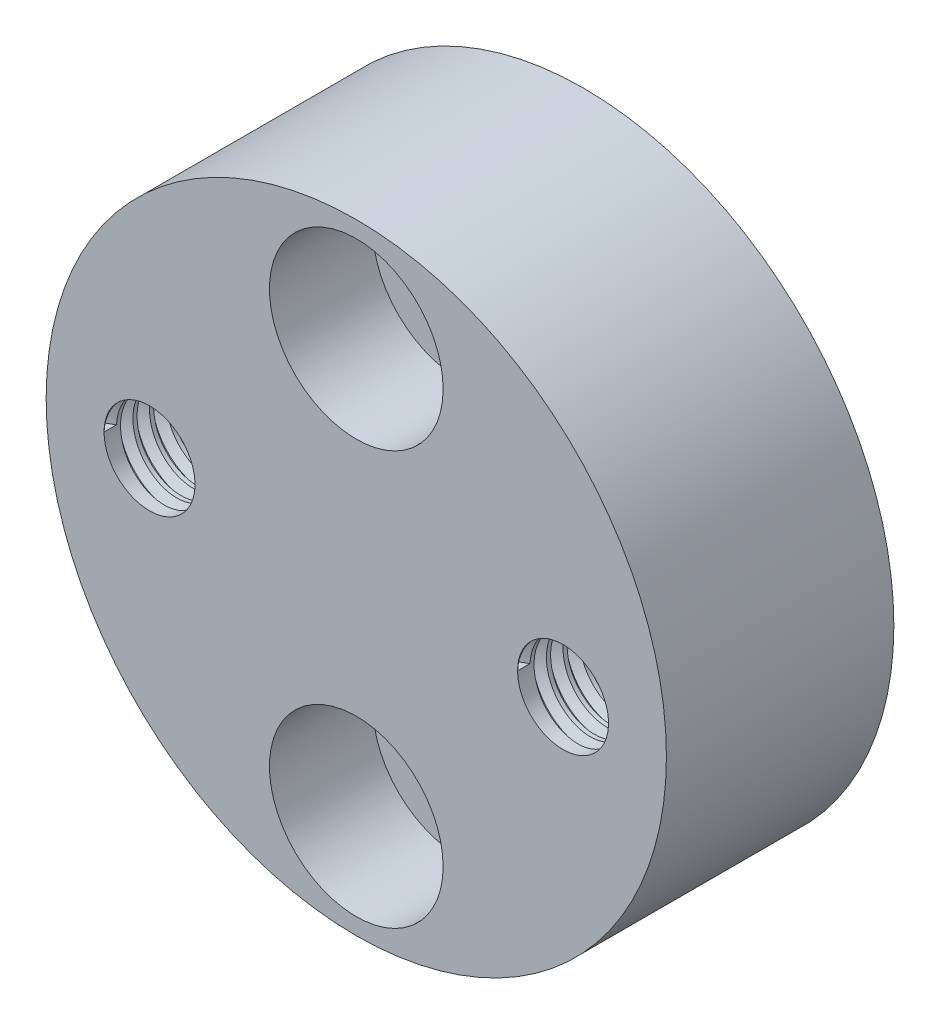
SolidWorks part; units mm, degrees
ref_plane "Ebene vorne" through (0, 0, 0) normal (0, 0, 1) x (1, 0, 0)
ref_plane "Ebene oben" through (0, 0, 0) normal (0, 1, 0) x (1, 0, 0)
ref_plane "Ebene rechts" through (0, 0, 0) normal (1, 0, 0) x (0, 0, -1)
sketch "Skizze1" plane through (0, 0, 0) normal (0, 0, 1) x (1, 0, 0)
  circle A0 centre (0, 0) radius 15
  dimension "D1" = 30
extrude "Aufsatz-Linear austragen1" add sketch "Skizze1" along normal blind 11
sketch "Skizze2" plane through (0, 0, 11) normal (0, 0, 1) x (1, 0, 0)
  circle A0 centre (0, 10) radius 2.5
  circle A1 centre (10, 0) radius 2.2
  circle A2 centre (0, -10) radius 2.5
  circle A3 centre (-10, 0) radius 2.2
  point P11 (0, 0)
  dimension "D1" = 4.4
  dimension "D2" = 5
  dimension "D3" = 4.4
  dimension "D4" = 5
  dimension "D5" = 10
  dimension "D6" = 10
  dimension "D7" = 10
  dimension "D8" = 10
extrude "Schnitt-Linear austragen1" cut sketch "Skizze2" against normal blind 33
sketch "Skizze3" plane through (0, 0, 11) normal (0, 0, 1) x (1, 0, 0)
  circle A0 centre (0, 10) radius 4.2
  circle A1 centre (0, -10) radius 4.2
  dimension "D1" = 8.4
  dimension "D2" = 8.4
extrude "Schnitt-Linear austragen2" cut sketch "Skizze3" against normal blind 5
thread "Gewinde1" pitch 0.8 method cut profile "Gewindeprofil1" start angle 0, offset 0, length 20, pitch 0.8, diameter 4.4
ref_plane "Ebene1" through (-12.2, 0, 11) normal (0, -1, 0) x (-1, 0, 0)
sketch "Gewindeprofil1" plane through (-12.2, 0, 11) normal (0, -1, 0) x (-1, 0, 0)
  line L0 (0, 0) -> (0, 0.8) construction
  line L1 (0, 0) -> (0.433, 0.25)
  line L2 (0.433, 0.25) -> (0.433, 0.35)
  line L3 (0.433, 0.35) -> (0, 0.6)
  line L4 (0.433, 0.3) -> (0, 0.3) construction
  line L11 (0, 0) -> (0, 0.6)
  point P2 (0, 0)
  dimension "Pitch" = 0.8
  dimension "Profile_Angle" = 60
  dimension "Profile_Land" = 0.1
  dimension "Profile_Height" = 0.433
thread "Gewinde2" pitch 0.8 method cut profile "Gewindeprofil2" start angle 0, offset 0, length 20, pitch 0.8, diameter 4.4
ref_plane "Ebene2" through (7.8, 0, 11) normal (0, -1, 0) x (-1, 0, 0)
sketch "Gewindeprofil2" plane through (7.8, 0, 11) normal (0, -1, 0) x (-1, 0, 0)
  line L0 (0, 0) -> (0, 0.8) construction
  line L1 (0, 0) -> (0.433, 0.25)
  line L2 (0.433, 0.25) -> (0.433, 0.35)
  line L3 (0.433, 0.35) -> (0, 0.6)
  line L4 (0.433, 0.3) -> (0, 0.3) construction
  line L11 (0, 0) -> (0, 0.6)
  point P2 (0, 0)
  dimension "Pitch" = 0.8
  dimension "Profile_Angle" = 60
  dimension "Profile_Land" = 0.1
  dimension "Profile_Height" = 0.433
